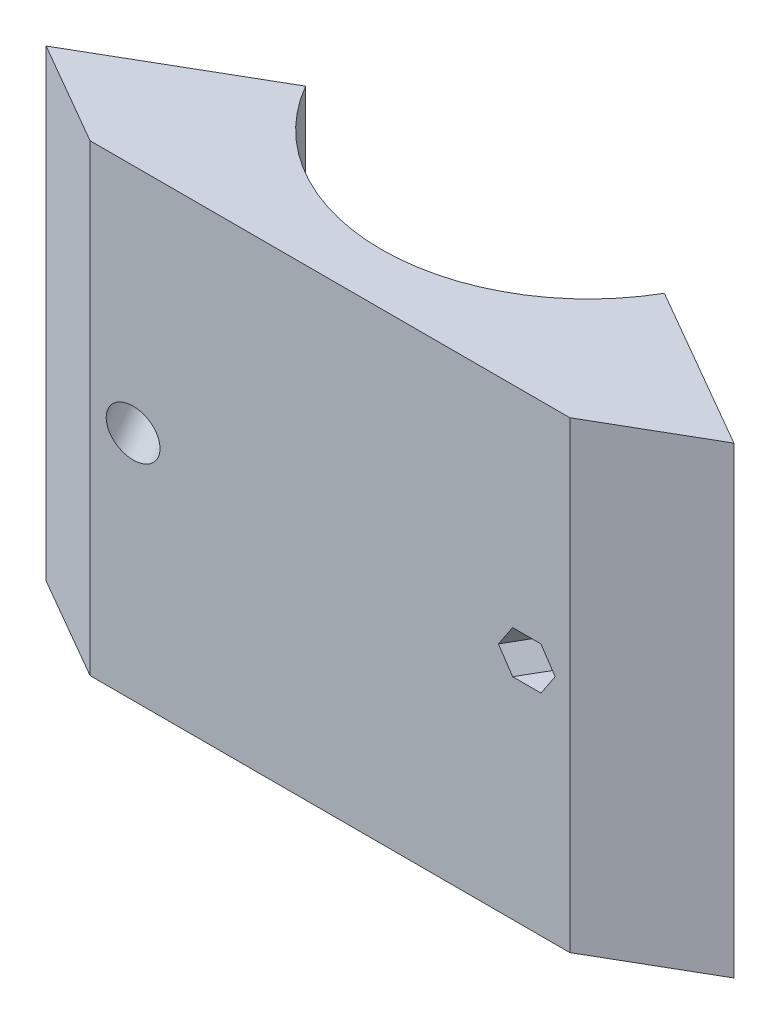
SolidWorks part; units mm, degrees
ref_plane "Front Plane" through (0, 0, 0) normal (0, 0, 1) x (1, 0, 0)
ref_plane "Top Plane" through (0, 0, 0) normal (0, 1, 0) x (1, 0, 0)
ref_plane "Right Plane" through (0, 0, 0) normal (1, 0, 0) x (0, 0, -1)
sketch "Sketch1" plane through (0, 0, 0) normal (0, 1, 0) x (1, 0, 0)
  line L20 (-84.8499, -19.3548) -> (-84.8499, -48.9881)
  line L21 (-84.8499, -48.9881) -> (-59.1867, -63.8048)
  line L22 (-59.1867, -63.8048) -> (59.1867, -63.8048)
  line L23 (59.1867, -63.8048) -> (84.8499, -48.9881)
  line L24 (84.8499, -48.9881) -> (84.8499, -19.3548)
  line L25 (84.8499, -19.3548) -> (25.6632, 83.1596)
  line L26 (25.6632, 83.1596) -> (0, 97.9763)
  line L27 (0, 97.9763) -> (-25.6632, 83.1596)
  line L28 (-25.6632, 83.1596) -> (-84.8499, -19.3548)
  line L29 (84.8499, -48.9881) -> (-55.2566, 31.9024)
  line L30 (55.2566, 31.9024) -> (-84.8499, -48.9881)
  line L31 (0, -63.8048) -> (0, 97.9763)
  circle A0 centre (0, 0) radius 51.1048
  point P13 (0, 0)
  point P20 (-44.2581, 25.5524)
  dimension "D1" = 102.2096
  dimension "D2" = 44.45
  dimension "D3" = 12.7
sketch "Sketch2" plane through (0, 0, 0) normal (0, 1, 0) x (1, 0, 0)
  line L0 (84.8499, -48.9881) -> (-55.2566, 31.9024) construction
  line L1 (59.1867, -63.8048) -> (84.8499, -48.9881) construction
  line L2 (-59.1867, -63.8048) -> (59.1867, -63.8048) construction
  line L3 (55.2566, 31.9024) -> (-84.8499, -48.9881) construction
  line L4 (-84.8499, -48.9881) -> (-59.1867, -63.8048) construction
  line L5 (84.8499, -48.9881) -> (-55.2566, 31.9024)
  line L6 (59.1867, -63.8048) -> (84.8499, -48.9881)
  line L7 (-59.1867, -63.8048) -> (59.1867, -63.8048)
  line L8 (55.2566, 31.9024) -> (-84.8499, -48.9881)
  line L9 (-84.8499, -48.9881) -> (-59.1867, -63.8048)
  line L10 (-64.0554, -36.9824) -> (-47.7703, -65.1891)
  line L13 (-59.0554, -45.6427) -> (-54.0757, -42.7677)
  line L14 (-54.0757, -42.7677) -> (-41.9299, -63.8048)
  line L15 (-41.9299, -63.8048) -> (-46.9096, -66.6798)
  line L16 (-46.9096, -66.6798) -> (-47.7703, -65.1891)
  line L17 (0, -62.865) -> (0, 62.865) construction
  line L21 (-64.0554, -36.9824) -> (-67.0865, -38.7324)
  line L22 (67.0865, -38.7324) -> (64.0554, -36.9824)
  line L23 (-46.9096, -66.6798) -> (-47.7703, -65.1891)
  line L24 (-61.0243, -35.2324) -> (-43.8785, -64.9298)
  line L25 (-61.0243, -35.2324) -> (-64.0554, -36.9824)
  circle A0 centre (0, 0) radius 51.1048 construction
  circle A1 centre (0, 0) radius 51.1048
  point P11 (-44.2581, -25.5524)
  point P21 (-42.3126, -67.6421)
  point P22 (0, 0)
  dimension "D1" = 22.86
  dimension "D3" = 5.75
  dimension "D4" = 10
  dimension "D2" = 3.5
extrude "Boss-Extrude1" add sketch "Sketch1" along normal mid plane 114.3 contours A0 L30 L21 L22 L31 | A0 L31 L22 L23 L29 region at (-42.3912, 0, 50.0899) region at (42.3912, 0, 50.0899)
revolve "Cut-Revolve7" cut sketch "Sketch2" angle 360 about L10 region at (-46.2293, 0, 64.8686) region at (-52.0172, 0, 54.2795) region at (-60.0399, 0, 40.4375)
revolve "Cut-Revolve8" cut sketch "Sketch2<7>" angle 360 about L10 region at (-49.1291, 0, 53.5649)
sketch "Sketch2<7>" plane through (0, 0, 0) normal (0, 1, 0) x (1, 0, 0) same geometry as "Sketch2"
mirror "Mirror1" about plane through (0, 0, 0) normal (1, 0, 0) of "Cut-Revolve7"
sketch "Sketch3" plane through (0, 0, 0) normal (0.5, 0, -0.866) x (-0.866, 0, -0.5)
  line L1 (-76.9959, 5.25) -> (-80.027, 0)
  line L2 (-80.027, 0) -> (-76.9959, -5.25)
  line L3 (-76.9959, -5.25) -> (-70.9337, -5.25)
  line L4 (-70.9337, -5.25) -> (-67.9026, 0)
  line L5 (-67.9026, 0) -> (-70.9337, 5.25)
  line L6 (-70.9337, 5.25) -> (-76.9959, 5.25)
  circle A0 centre (-73.9648, 0) radius 3.5 construction
  circle A1 centre (-73.9648, 0) radius 3.5
  circle A2 centre (-73.9648, 0) radius 5.25 construction
  dimension "D1" = 10.5
extrude "Cut-Extrude1" cut sketch "Sketch3" against normal through all from offset 10 offset against normal yes
ref_axis "Axis1" through (0, 57.15, 0) along (0, -1, 0)
equation "\"Tube_Diameter_With_Tolerance\"= 4.024"
equation "\"Vertical_Surface_Height\"= 1.75in"
equation "\"D1@Sketch1\"=\"Tube_Diameter_With_Tolerance\""
equation "\"D2@Sketch1\"=\"Vertical_Surface_Height\""
equation "\"Offset_From_Diameter\"= .5in"
equation "\"D3@Sketch1\"=\"Offset_From_Diameter\""
equation "\"Thread_Center\"= 1.8 * \"Offset_From_Diameter\""
equation "\"M6_Thread_Clearance\"= 7mm"
equation "\"M6_Head_Clearance\"= 11.5mm"
equation "\"M6_Nut_Flat_To_Flat\"= 10.5mm"
equation "\"Nut_Start\"= 10mm"
equation "\"D1@Sketch2\"=\"Thread_Center\""
equation "\"D3@Sketch2\"=\"M6_Head_Clearance\"/2"
equation "\"D4@Sketch2\"=\"Nut_Start\""
equation "\"Length\"= 4.5in"
equation "\"D1@Boss-Extrude1\"=\"Length\""
equation "\"D2@Sketch2\"=\"M6_Thread_Clearance\"/2"
equation "\"D1@Sketch3\"=\"M6_Nut_Flat_To_Flat\""
equation "\"D19@Cut-Extrude1\"=\"Nut_Start\""
